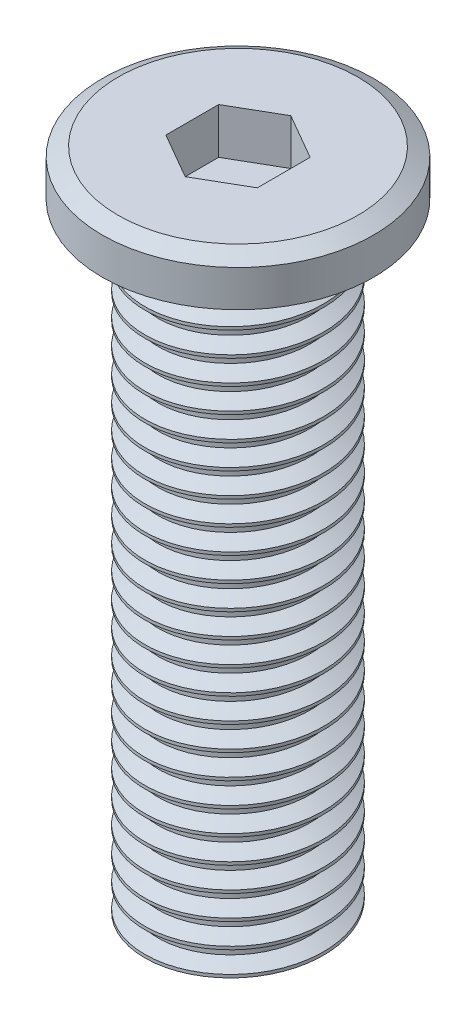
SolidWorks part; units mm, degrees
ref_plane "Front Plane" through (0, 0, 0) normal (0, 0, 1) x (1, 0, 0)
ref_plane "Top Plane" through (0, 0, 0) normal (0, 1, 0) x (1, 0, 0)
ref_plane "Right Plane" through (0, 0, 0) normal (1, 0, 0) x (0, 0, -1)
sketch "Sketch1" plane through (0, 0, 0) normal (0, 1, 0) x (1, 0, 0)
  circle A0 centre (0, 0) radius 4.45
  dimension "D1" = 8.9
extrude "Boss-Extrude1" add sketch "Sketch1" along normal blind 1.5
chamfer "Chamfer2" distance 0.3 angle 60 1 edges at (0, 1.5, 4.45) first distance on face at (0, 1.5, 4.45)
sketch "Sketch8" plane through (0, 1.5, 0) normal (0, 1, 0) x (1, 0, 0)
  line L1 (0, 1.7321) -> (-1.5, 0.866)
  line L2 (-1.5, 0.866) -> (-1.5, -0.866)
  line L3 (-1.5, -0.866) -> (0, -1.7321)
  line L4 (0, -1.7321) -> (1.5, -0.866)
  line L5 (1.5, -0.866) -> (1.5, 0.866)
  line L6 (1.5, 0.866) -> (0, 1.7321)
  circle A0 centre (0, 0) radius 1.5 construction
  dimension "D1" = 3
  dimension "D2" = 1.5
extrude "Cut-Extrude1" cut sketch "Sketch8" against normal blind 3
sketch "Sketch3" plane through (0, 0, 0) normal (0, -1, 0) x (1, 0, 0)
  circle A0 centre (0, 0) radius 2.5
  dimension "D1" = 5
extrude "Boss-Extrude2" add sketch "Sketch3" along normal blind 20
thread "Thread1" pitch 0.8 method extrude profile "Thread Profile2" start angle 0, offset 0, length 0, pitch 0.8, diameter 5
ref_plane "Plane2" through (-2.5, 0, 0) normal (0, 0, 1) x (-1, 0, 0)
sketch "Thread Profile2" plane through (-2.5, 0, 0) normal (0, 0, 1) x (-1, 0, 0)
  line L0 (0, 0) -> (0, 0.8) construction
  line L1 (0, 0) -> (0.433, 0.25)
  line L2 (0.433, 0.25) -> (0.433, 0.35)
  line L3 (0.433, 0.35) -> (0, 0.6)
  line L4 (0.433, 0.3) -> (0, 0.3) construction
  line L11 (0, 0) -> (0, 0.6)
  point P2 (0, 0)
  dimension "Pitch" = 0.8
  dimension "Profile_Angle" = 60
  dimension "Profile_Land" = 0.1
  dimension "Profile_Height" = 0.433
